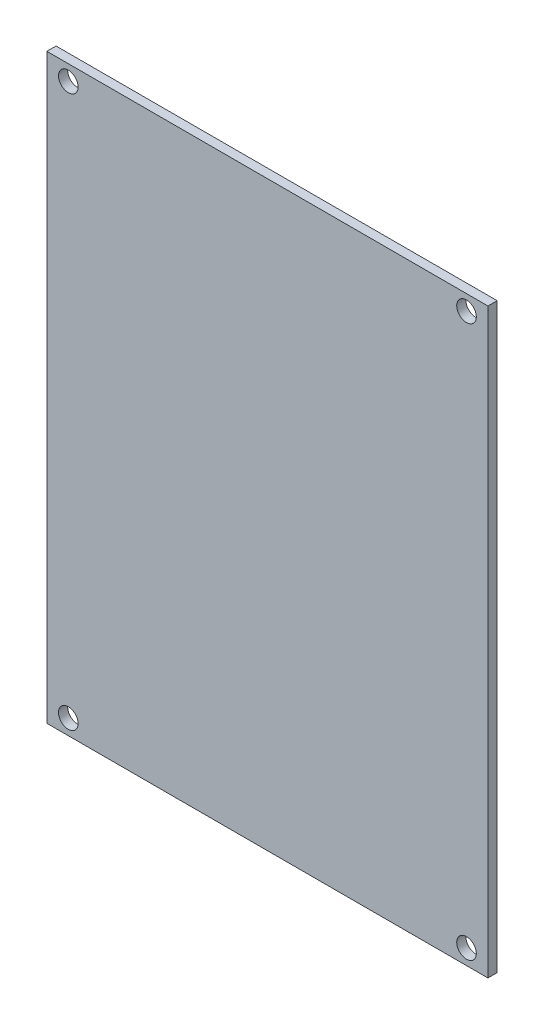
SolidWorks part; units mm, degrees
material "ABS"
ref_plane "正面" through (0, 0, 0) normal (0, 0, 1) x (1, 0, 0)
ref_plane "平面" through (0, 0, 0) normal (0, 1, 0) x (1, 0, 0)
ref_plane "右側面" through (0, 0, 0) normal (1, 0, 0) x (0, 0, -1)
sketch "ｽｹｯﾁ1" plane through (0, 0, 0) normal (0, 0, 1) x (1, 0, 0)
  line L1 (36, -47.5) -> (-36, -47.5)
  line L2 (36, -47.5) -> (36, 47.5)
  line L3 (36, 47.5) -> (-36, 47.5)
  line L4 (-36, -47.5) -> (-36, 47.5)
  line L5 (36, -47.5) -> (-36, 47.5) construction
  line L6 (36, 47.5) -> (-36, -47.5) construction
  line L7 (32.5, -45) -> (-32.5, -45) construction
  line L8 (32.5, -45) -> (32.5, 45) construction
  line L9 (32.5, 45) -> (-32.5, 45) construction
  line L10 (-32.5, -45) -> (-32.5, 45) construction
  line L11 (32.5, -45) -> (-32.5, 45) construction
  line L12 (32.5, 45) -> (-32.5, -45) construction
  circle A0 centre (-32.5, 45) radius 1.6
  circle A1 centre (32.5, 45) radius 1.6
  circle A2 centre (-32.5, -45) radius 1.6
  circle A3 centre (32.5, -45) radius 1.6
  point P0 (0, 0)
  point P6 (0, 0)
  dimension "D3" = 3.2
  dimension "D1" = 95
  dimension "D2" = 72
  dimension "D4" = 65
  dimension "D5" = 90
extrude "ﾎﾞｽ - 押し出し1" add sketch "ｽｹｯﾁ1" along normal blind 1.5
